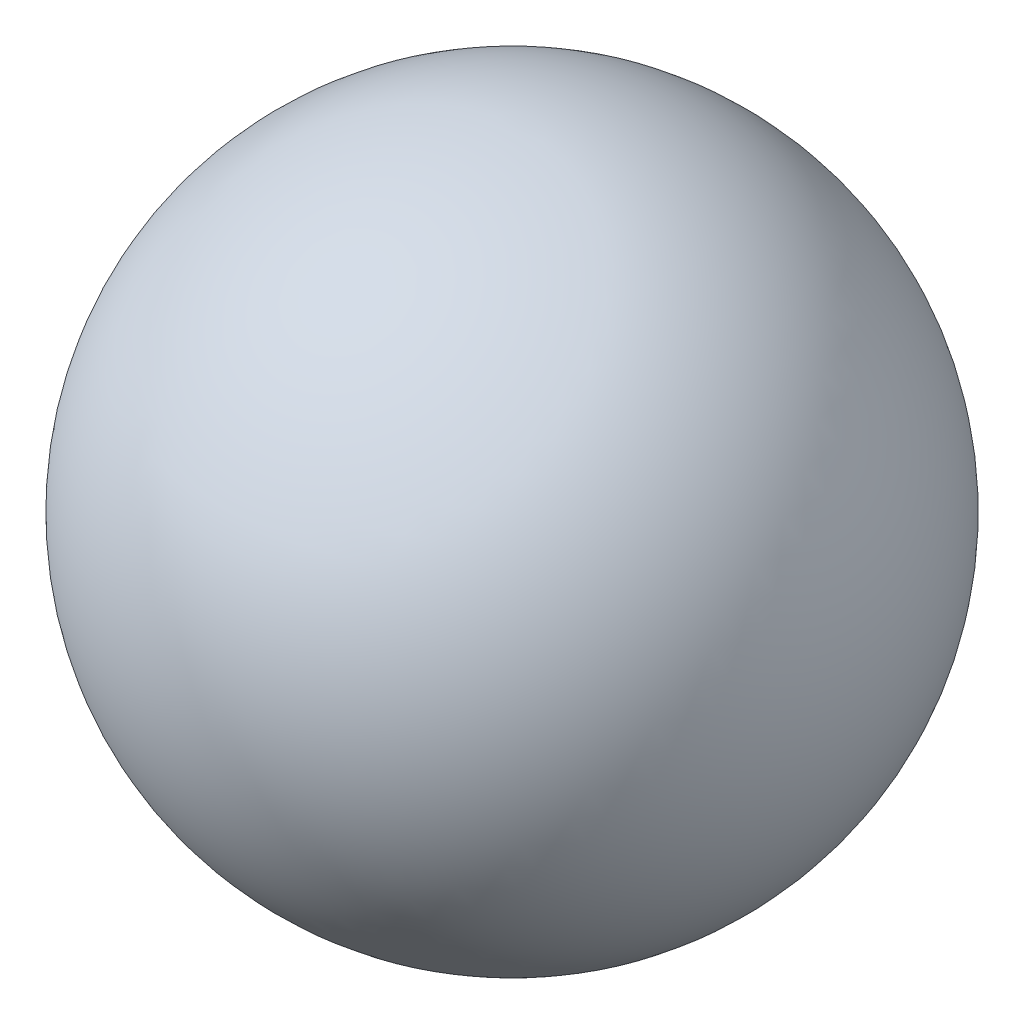
SolidWorks part; units mm, degrees
ref_plane "Front" through (0, 0, 0) normal (0, 0, 1) x (1, 0, 0)
ref_plane "Top" through (0, 0, 0) normal (0, 1, 0) x (1, 0, 0)
ref_plane "Right" through (0, 0, 0) normal (1, 0, 0) x (0, 0, -1)
sketch "Sketch2" plane through (0, 0, 0) normal (1, 0, 0) x (0, 0, -1)
  line L0 (0, -2.16) -> (0, 2.16)
  circle A0 centre (0, 0) radius 2.16 construction
  arc A1 (0, 2.16) -> (0, -2.16) centre (0, 0) cw
  dimension "D1" = 4.32
revolve "Revolve1" add sketch "Sketch2" angle 360 about L0 region at (0, 0, -0.9167)
sketch "Right Plane Cut Guide" plane through (0, 0, 0) normal (1, 0, 0) x (0, 0, -1)
  line L0 (-1.25, 2.16) -> (1.25, 2.16)
  line L1 (1.25, 2.16) -> (1.6642, 1.7458)
  line L2 (2.25, 0.3316) -> (2.25, -0.3316)
  line L3 (-1.25, 2.16) -> (-1.6642, 1.7458)
  line L4 (-2.25, 0.3316) -> (-2.25, -0.3316)
  line L5 (0, 0) -> (0, 2.16) construction
  line L6 (0, 0) -> (-2.25, 0) construction
  line L7 (-1.25, -2.16) -> (-1.6642, -1.7458)
  line L8 (-1.25, -2.16) -> (1.25, -2.16)
  line L9 (1.25, -2.16) -> (1.6642, -1.7458)
  arc A0 (1.6642, -1.7458) -> (2.25, -0.3316) centre (0.25, -0.3316) ccw
  arc A1 (-1.6642, -1.7458) -> (-2.25, -0.3316) centre (-0.25, -0.3316) cw
  arc A2 (1.6642, 1.7458) -> (2.25, 0.3316) centre (0.25, 0.3316) cw
  circle A3 centre (0, 0) radius 2.25 construction
  arc A4 (-1.6642, 1.7458) -> (-2.25, 0.3316) centre (-0.25, 0.3316) ccw
  circle A5 centre (0, 0) radius 2.16 construction
  circle A6 centre (0, 0) radius 2.16 construction
  point P5 (0, 2.25)
  point P14 (2.25, 0)
  point P17 (2.25, -1.16)
  point P20 (-2.25, -1.16)
  point P23 (2.25, 1.16)
  point P26 (-2.25, 1.16)
  dimension "D1" = 4.5
  dimension "D5" = 2
  dimension "D2" = 45
  dimension "D3" = 1
